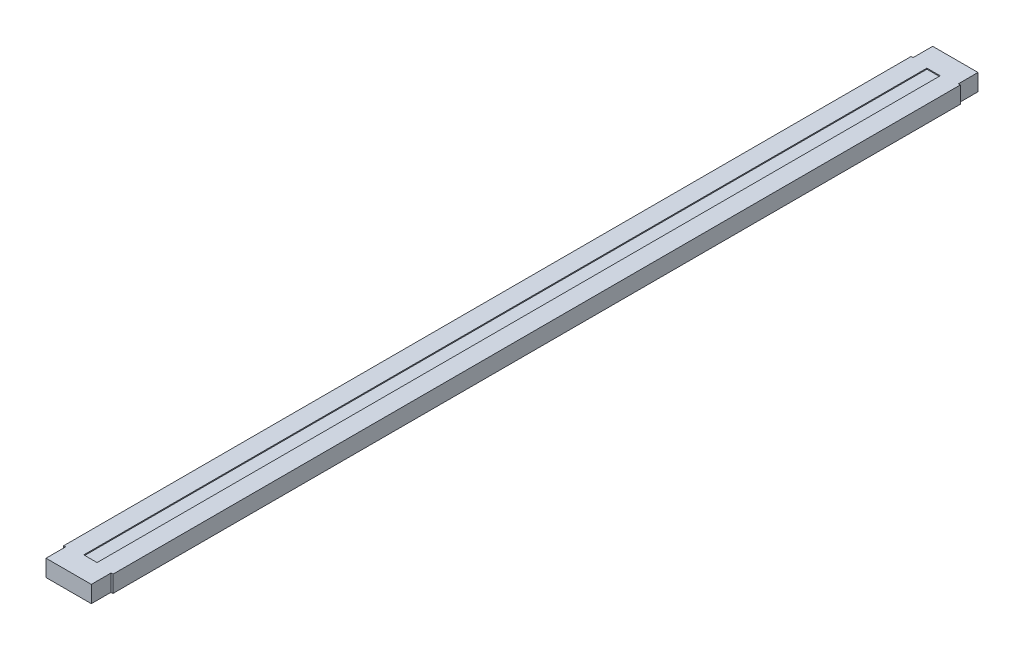
SolidWorks part; units mm, degrees
ref_plane "Front Plane" through (0, 0, 0) normal (0, 0, 1) x (1, 0, 0)
ref_plane "Top Plane" through (0, 0, 0) normal (0, 1, 0) x (1, 0, 0)
ref_plane "Right Plane" through (0, 0, 0) normal (1, 0, 0) x (0, 0, -1)
sketch "Sketch1" plane through (0, 0, 0) normal (0, 0, 1) x (1, 0, 0)
  line L1 (-6.35, -2.159) -> (6.35, -2.159)
  line L2 (-6.35, -2.159) -> (-6.35, 2.159)
  line L3 (-6.35, 2.159) -> (6.35, 2.159)
  line L4 (6.35, -2.159) -> (6.35, 2.159)
  line L5 (-6.35, -2.159) -> (6.35, 2.159) construction
  line L6 (-6.35, 2.159) -> (6.35, -2.159) construction
  point P0 (0, 0)
  dimension "D1" = 4.318
  dimension "D2" = 12.7
extrude "Boss-Extrude1" add sketch "Sketch1" along normal blind 228.6
sketch "Sketch2" plane through (0, 2.159, 0) normal (0, 1, 0) x (1, 0, 0)
  line L0 (1.7145, -114.3) -> (6.35, -114.3) construction
  line L1 (-1.7145, -5.6134) -> (1.7145, -5.6134)
  line L2 (-1.7145, -5.6134) -> (-1.7145, -222.9866)
  line L3 (-1.7145, -222.9866) -> (1.7145, -222.9866)
  line L4 (1.7145, -5.6134) -> (1.7145, -222.9866)
  line L5 (6.35, -228.6) -> (6.35, 0) construction
  line L6 (-1.7145, -114.3) -> (-6.35, -114.3) construction
  line L7 (-6.35, -228.6) -> (-6.35, 0) construction
  dimension "D1" = 3.429
  dimension "D2" = 217.3732
extrude "Cut-Extrude1" cut sketch "Sketch2" against normal blind 0.254
sketch "Sketch3" plane through (0, 2.159, 0) normal (0, 1, 0) x (1, 0, 0)
  line L1 (-6.35, -228.6) -> (-5.842, -228.6)
  line L2 (-6.35, -228.6) -> (-6.35, -223.52)
  line L3 (-6.35, -223.52) -> (-5.842, -223.52)
  line L4 (-5.842, -228.6) -> (-5.842, -223.52)
  dimension "D1" = 0.508
  dimension "D2" = 5.08
extrude "Cut-Extrude2" cut sketch "Sketch3" against normal through all
ref_plane "Plane1" through (0, 0, 114.3) normal (0, 0, -1) x (-1, 0, 0)
mirror "Mirror1" about plane through (0, 0, 114.3) normal (0, 0, -1) of "Cut-Extrude2"
mirror "Mirror2" about plane through (0, 0, 0) normal (1, 0, 0) of "Mirror1", "Cut-Extrude2"
